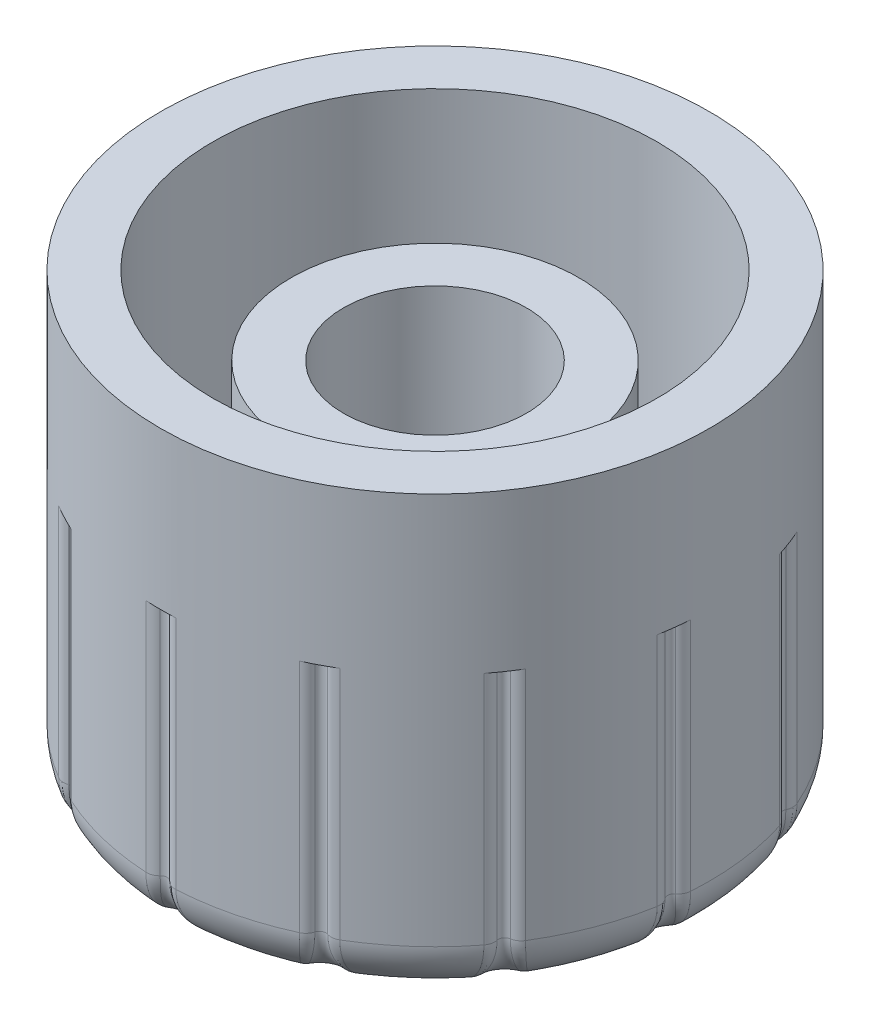
SolidWorks part; units mm, degrees
ref_plane "Front Plane" through (0, 0, 0) normal (0, 0, 1) x (1, 0, 0)
ref_plane "Top Plane" through (0, 0, 0) normal (0, 1, 0) x (1, 0, 0)
ref_plane "Right Plane" through (0, 0, 0) normal (1, 0, 0) x (0, 0, -1)
sketch "Sketch1" plane through (0, 0, 0) normal (0, 1, 0) x (1, 0, 0)
  circle A0 centre (0, 0) radius 10.5
  dimension "D1" = 21
extrude "Boss-Extrude1" add sketch "Sketch1" along normal blind 2
sketch "Sketch2" plane through (0, 0, 0) normal (0, 1, 0) x (1, 0, 0)
  circle A0 centre (0, 0) radius 8.5
  circle A1 centre (0, 0) radius 10.5
  dimension "D1" = 17
  dimension "D2" = 21
extrude "Boss-Extrude2" add sketch "Sketch2" along normal blind 17
sketch "Sketch3" plane through (0, 0, 0) normal (0, 1, 0) x (1, 0, 0)
  circle A0 centre (0, 0) radius 3.5
  circle A1 centre (0, 0) radius 5.5
  dimension "D1" = 7
  dimension "D2" = 11
extrude "Boss-Extrude3" add sketch "Sketch3" along normal blind 14
sketch "Sketch4" plane through (0, 0, 0) normal (0, 1, 0) x (1, 0, 0)
  line L0 (2.4495, 2.5) -> (2.4495, -2.5)
  circle A0 centre (0, 0) radius 3.5
  dimension "D1" = 7
  dimension "D2" = 5
extrude "Boss-Extrude4" add sketch "Sketch4" along normal blind 12 contours L0 A0 region at (2.8756, 0, 0)
sketch "Sketch5" plane through (0, 0, 0) normal (0, -1, 0) x (1, 0, 0)
  line L0 (-0.003, 10.5) -> (4.8769, 9.2987) construction
  line L1 (4.8769, 9.2987) -> (8.6396, 5.9671) construction
  line L2 (8.6396, 5.9671) -> (10.4231, 1.2686) construction
  line L3 (10.4231, 1.2686) -> (9.8187, -3.7206) construction
  line L4 (9.8187, -3.7206) -> (6.965, -7.8574) construction
  line L5 (6.965, -7.8574) -> (2.5157, -10.1942) construction
  line L6 (2.5157, -10.1942) -> (-2.5099, -10.1956) construction
  line L7 (-2.5099, -10.1956) -> (-6.9605, -7.8613) construction
  line L8 (-6.9605, -7.8613) -> (-9.8166, -3.7261) construction
  line L9 (-9.8166, -3.7261) -> (-10.4238, 1.2627) construction
  line L10 (-10.4238, 1.2627) -> (-8.643, 5.9622) construction
  line L11 (-8.643, 5.9622) -> (-4.8822, 9.2959) construction
  line L12 (-4.8822, 9.2959) -> (-0.003, 10.5) construction
  circle A0 centre (-0.003, 10.5) radius 0.25
  circle A1 centre (0, 0) radius 10.5 construction
  circle A2 centre (4.8769, 9.2987) radius 0.25
  circle A3 centre (8.6396, 5.9671) radius 0.25
  circle A4 centre (10.4231, 1.2686) radius 0.25
  circle A5 centre (9.8187, -3.7206) radius 0.25
  circle A6 centre (6.965, -7.8574) radius 0.25
  circle A7 centre (2.5157, -10.1942) radius 0.25
  circle A8 centre (-2.5099, -10.1956) radius 0.25
  circle A9 centre (-6.9605, -7.8613) radius 0.25
  circle A10 centre (-9.8166, -3.7261) radius 0.25
  circle A11 centre (-10.4238, 1.2627) radius 0.25
  circle A12 centre (-8.643, 5.9622) radius 0.25
  circle A13 centre (-4.8822, 9.2959) radius 0.25
  dimension "D1" = 0.5
extrude "Cut-Extrude1" cut sketch "Sketch5" against normal blind 11
fillet "Fillet1" radius 2 26 edges at (4.7608, 0, 9.0773) (6.9605, 0, 7.8613) (8.4339, 0, 5.8251) (9.8166, 0, 3.7261) (10.1749, 0, 1.2384) (10.4238, 0, -1.2627) (9.585, 0, -3.632) (8.643, 0, -5.9622) (6.7992, 0, -7.6703) (4.8822, 0, -9.2959) (2.4558, 0, -9.9515) (0.003, 0, -10.5) (-2.4502, 0, -9.9529) (-4.8769, 0, -9.2987) (-6.7948, 0, -7.6742) (-8.6396, 0, -5.9671) (-9.5829, 0, -3.6374) (-10.4231, 0, -1.2686) (-10.1756, 0, 1.2326) (-9.8187, 0, 3.7206) (-8.4372, 0, 5.8203) (-6.965, 0, 7.8574) (-4.766, 0, 9.0746) (-2.5157, 0, 10.1942) (-0.0029, 0, 10.25) (2.5099, 0, 10.1956)
fillet "Fillet2" radius 0.5 52 edges at (-3.9569, 0.4357, 8.9068) (-5.0871, 0.4357, 8.3132) (-4.6595, 6.5, 9.4095) (-5.1022, 6.5, 9.177) (-7.6429, 0.4357, 6.0477) (-8.3677, 0.4357, 4.9969) (-9.5779, 0.4357, 1.8032) (-9.7314, 0.4357, 0.5358) (-9.3188, 0.4357, -2.8545) (-8.8658, 0.4357, -4.048) (-6.9249, 0.4357, -6.8582) (-5.9691, 0.4357, -7.7044) (-2.9445, 0.4357, -9.2907) (-1.7049, 0.4357, -9.5959) (1.7104, 0.4357, -9.5949) (2.9498, 0.4357, -9.2891) (5.9735, 0.4357, -7.701) (6.9288, 0.4357, -6.8542) (8.8681, 0.4357, -4.0429) (9.3204, 0.4357, -2.8491) (9.7311, 0.4357, 0.5414) (9.5769, 0.4357, 1.8086) (8.3649, 0.4357, 5.0016) (7.6394, 0.4357, 6.0521) (5.0824, 0.4357, 8.3161) (3.9518, 0.4357, 8.909) (0.6355, 0.4357, 9.7254) (-0.6411, 0.4357, 9.7251) (-8.4986, 6.5, 6.1663) (-8.7825, 6.5, 5.7548) (-10.3908, 6.5, 1.5105) (-10.4509, 6.5, 1.0141) (-9.9025, 6.5, -3.4914) (-9.7251, 6.5, -3.9588) (-7.1457, 6.5, -7.6934) (-6.7714, 6.5, -8.0248) (-2.7519, 6.5, -10.133) (-2.2665, 6.5, -10.2525) (2.2723, 6.5, -10.2512) (2.7577, 6.5, -10.1314) (6.776, 6.5, -8.021) (7.1501, 6.5, -7.6893) (9.7274, 6.5, -3.9533) (9.9045, 6.5, -3.4857) (10.4503, 6.5, 1.0201) (10.3899, 6.5, 1.5164) (8.7792, 6.5, 5.7598) (8.4951, 6.5, 6.1711) (5.0969, 6.5, 9.1799) (4.6542, 6.5, 9.4122) (0.247, 6.5, 10.4971) (-0.253, 6.5, 10.497)
fillet "Fillet3" radius 2 1 edges at (0, 2, 8.5)
fillet "Fillet4" radius 1 1 edges at (0, 2, 5.5)
